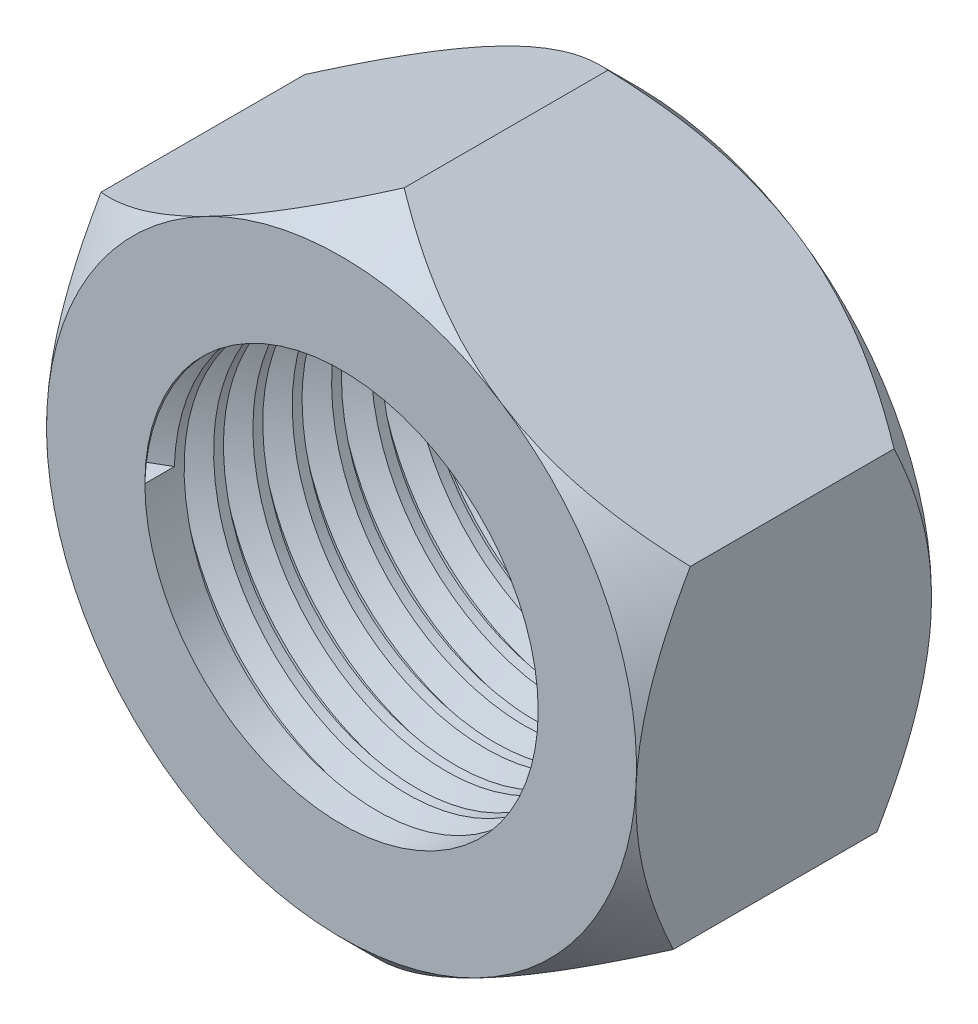
SolidWorks part; units mm, degrees
material "AISI 1020"
ref_plane "Front Plane" through (0, 0, 0) normal (0, 0, 1) x (1, 0, 0)
ref_plane "Top Plane" through (0, 0, 0) normal (0, 1, 0) x (1, 0, 0)
ref_plane "Right Plane" through (0, 0, 0) normal (1, 0, 0) x (0, 0, -1)
sketch "Sketch1" plane through (0, 0, 0) normal (0, 0, 1) x (1, 0, 0)
  line L1 (-15.4145, -7.899) -> (-0.8665, -17.2988)
  line L2 (-0.8665, -17.2988) -> (14.548, -9.3998)
  line L3 (14.548, -9.3998) -> (15.4145, 7.899)
  line L4 (15.4145, 7.899) -> (0.8665, 17.2988)
  line L5 (0.8665, 17.2988) -> (-14.548, 9.3998)
  line L6 (-14.548, 9.3998) -> (-15.4145, -7.899)
  circle A0 centre (0, 0) radius 15 construction
  circle A1 centre (0, 0) radius 10
  dimension "D1" = 20
  dimension "D2" = 30
extrude "Boss-Extrude2" add sketch "Sketch1" against normal blind 15
sketch "Sketch2" plane through (0, 0, 0) normal (0, 0, 1) x (1, 0, 0)
  line L0 (15.4145, 7.899) -> (0.8665, 17.2988) construction
  circle A0 centre (0, 0) radius 15
sketch "Sketch3" plane through (0, 0, -15) normal (0, 0, -1) x (-1, 0, 0)
  line L0 (14.548, 9.3998) -> (15.4145, -7.899) construction
  circle A0 centre (0, 0) radius 15
extrude "Cut-Extrude3" cut sketch "Sketch2" against normal blind 15 draft 45 flip side to cut
extrude "Cut-Extrude4" cut sketch "Sketch3" against normal blind 15 draft 45 flip side to cut
thread "Thread1" pitch 2 method cut profile "Thread Profile3" start angle 0, offset 0, length 0, pitch 2, diameter 20
ref_plane "Plane3" through (-10, 0, 0) normal (0, -1, 0) x (-1, 0, 0)
sketch "Thread Profile3" plane through (-10, 0, 0) normal (0, -1, 0) x (-1, 0, 0)
  line L0 (0, 0) -> (0, 2) construction
  line L1 (0, 0) -> (1.0825, 0.625)
  line L2 (1.0825, 0.625) -> (1.0825, 0.875)
  line L3 (1.0825, 0.875) -> (0, 1.5)
  line L4 (1.0825, 0.75) -> (0, 0.75) construction
  line L11 (0, 0) -> (0, 1.5)
  point P2 (0, 0)
  dimension "Pitch" = 2
  dimension "Profile_Angle" = 60
  dimension "Profile_Land" = 0.25
  dimension "Profile_Height" = 1.0825
